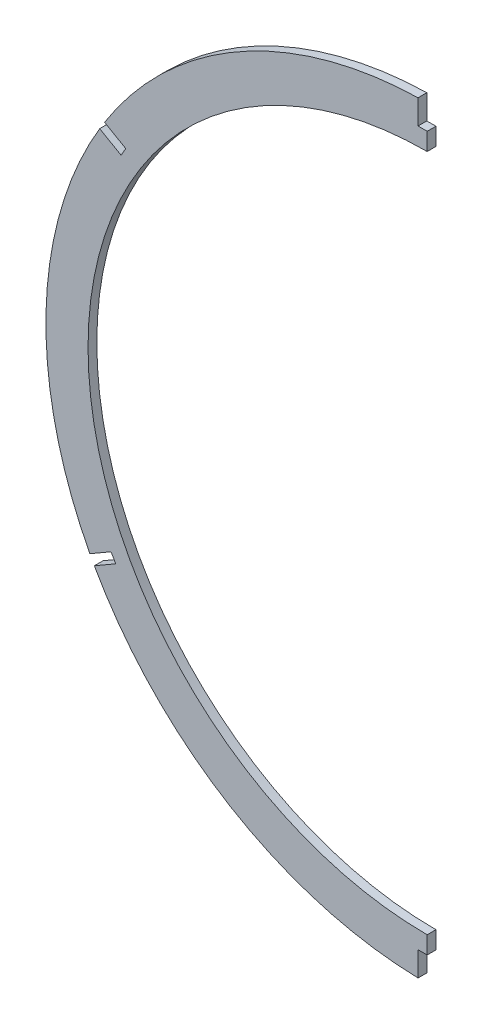
SolidWorks part; units mm, degrees
material "Balsa"
ref_plane "Front Plane" through (0, 0, 0) normal (0, 0, 1) x (1, 0, 0)
ref_plane "Top Plane" through (0, 0, 0) normal (0, 1, 0) x (1, 0, 0)
ref_plane "Right Plane" through (0, 0, 0) normal (1, 0, 0) x (0, 0, -1)
sketch "Sketch1" plane through (0, 0, 0) normal (0, 0, 1) x (1, 0, 0)
  line L0 (0, 0) -> (0, 499.9473) construction
  line L1 (0, -114.7984) -> (0, -129.4545) construction
  line L2 (0, -374.4718) -> (0, 404.2655) construction
  line L3 (-1.651, 142.9921) -> (-1.651, 150.6121) construction
  line L4 (1.651, 142.9921) -> (1.651, 150.6121) construction
  line L5 (-1.651, 142.9921) -> (1.651, 142.9921) construction
  line L6 (136.2041, -53.806) -> (0.0002, 24.7625) construction
  line L7 (-136.2076, -53.7991) -> (0.0002, 24.7625) construction
  line L8 (136.2041, -53.806) -> (0.0002, 24.7625) construction
  line L9 (-136.2076, -53.7991) -> (0.0002, 24.7625) construction
  line L10 (-125.0584, -45.4626) -> (-118.4576, -41.6554) construction
  line L11 (-123.6259, -48.4483) -> (-116.8078, -44.5157) construction
  line L12 (-118.4576, -41.6554) -> (-116.8078, -44.5157) construction
  line L13 (-124.1455, -48.7479) -> (-123.6847, -48.4822) construction
  line L14 (-123.6847, -48.4822) -> (-123.6259, -48.4483) construction
  line L15 (-125.7952, -45.8876) -> (-125.1113, -45.4931) construction
  line L16 (-125.1113, -45.4931) -> (-125.0584, -45.4626) construction
  line L17 (125.4797, -45.7137) -> (125.1075, -45.499) construction
  line L18 (123.8298, -48.5739) -> (123.6807, -48.488) construction
  line L19 (117.0223, -44.647) -> (118.6722, -41.7868) construction
  line L20 (123.6807, -48.488) -> (123.6228, -48.4545) construction
  line L21 (123.6228, -48.4545) -> (117.0223, -44.647) construction
  line L22 (125.1075, -45.499) -> (125.0554, -45.4689) construction
  line L23 (125.0554, -45.4689) -> (118.6722, -41.7868) construction
  line L24 (-107.079, -46.8884) -> (-120.3798, -54.5735)
  line L25 (-108.6638, -44.1348) -> (-121.9647, -51.8199)
  line L28 (-115.4206, -47.9666) -> (-121.9445, -51.7361) construction
  line L29 (-120.2754, -54.5131) -> (-108.646, -44.1245) construction
  line L30 (-114.4607, -49.3188) -> (-122.1124, -53.7399) construction
  line L31 (-113.7686, -50.8257) -> (-120.3665, -54.6379) construction
  line L32 (-115.4206, -47.9666) -> (-113.7686, -50.8257) construction
  line L33 (106.3137, -46.4532) -> (129.9098, -60.0883)
  line L34 (107.9004, -43.7007) -> (131.505, -57.3407)
  line L35 (129.9098, -60.0883) -> (131.505, -57.3407)
  line L36 (129.9098, -60.0883) -> (131.505, -57.3407) construction
  line L37 (107.9004, -43.7007) -> (131.505, -57.3407) construction
  line L38 (106.3137, -46.4532) -> (129.9098, -60.0883) construction
  line L39 (129.9098, -60.0883) -> (107.9004, -43.7007) construction
  line L40 (118.9051, -51.8945) -> (101.8722, -42.0519) construction
  line L41 (120.3631, -54.6438) -> (113.7655, -50.8313)
  line L42 (122.0152, -51.7848) -> (122.0057, -51.7794) construction
  line L43 (113.7655, -50.8313) -> (115.4176, -47.9723)
  line L44 (122.0057, -51.7794) -> (121.9413, -51.7421) construction
  line L45 (121.9413, -51.7421) -> (115.4176, -47.9723)
  line L46 (-108.6638, -44.1348) -> (-121.9647, -51.8199)
  line L47 (-107.079, -46.8884) -> (-120.3798, -54.5735)
  arc A0 (-1.651, 150.6121) -> (-125.0584, -45.4626) centre (0, 12.7) ccw
  circle A1 centre (0, 12.7) radius 120.904
  arc A2 (0, 150.622) -> (-1.651, 150.6121) centre (0, 12.7) ccw
  circle A3 centre (0, 12.7) radius 137.922 construction
  arc A4 (1.651, 150.6121) -> (0, 150.622) centre (0, 12.7) ccw
  arc A5 (-124.3508, -46.9604) -> (-123.6259, -48.4483) centre (0, 12.7) ccw
  arc A6 (-123.6259, -48.4483) -> (-121.9445, -51.7361) centre (0, 12.7) ccw
  arc A7 (-125.0584, -45.4626) -> (-124.3508, -46.9604) centre (0, 12.7) ccw
  arc A8 (124.3477, -46.9667) -> (125.0554, -45.4689) centre (0, 12.7) ccw
  arc A9 (125.0554, -45.4689) -> (1.651, 150.6121) centre (0, 12.7) ccw
  arc A10 (123.6228, -48.4545) -> (124.3477, -46.9667) centre (0, 12.7) ccw
  arc A11 (-121.9153, -51.7914) -> (-121.1641, -53.1919) centre (0, 12.7) ccw
  arc A12 (-120.3665, -54.6379) -> (120.3631, -54.6438) centre (0, 12.7) ccw
  arc A13 (-121.9445, -51.7361) -> (-121.9153, -51.7914) centre (0, 12.7) ccw
  arc A14 (-121.1641, -53.1919) -> (-120.3827, -54.6089) centre (0, 12.7) ccw
  arc A15 (-120.3827, -54.6089) -> (-120.397, -54.5834) centre (0, 12.7) ccw construction
  arc A16 (-120.397, -54.5834) -> (-120.3665, -54.6379) centre (0, 12.7) ccw construction
  arc A17 (120.3936, -54.5893) -> (121.0149, -53.4654) centre (0, 12.7) ccw construction
  arc A18 (121.9413, -51.7421) -> (123.6228, -48.4545) centre (0, 12.7) ccw
  arc A19 (120.3631, -54.6438) -> (120.3936, -54.5893) centre (0, 12.7) ccw construction
  arc A20 (121.0149, -53.4654) -> (121.9121, -51.7974) centre (0, 12.7) ccw construction
  arc A21 (121.9121, -51.7974) -> (121.9413, -51.7421) centre (0, 12.7) ccw construction
  spline S0 degree 3 poles (106.3137, -46.4532) (106.8426, -45.5357) (107.3715, -44.6182) (107.9004, -43.7007) knots 0 0 0 0 1 1 1 1 weights 1 1 1 1
  spline S1 degree 3 poles (-66.0123, 133.6164) (-70.0128, 131.4329) (-73.8716, 129.0699) (-81.3156, 123.9975) (-84.9009, 121.288) (-91.7995, 115.5249) (-95.113, 112.4712) (-99.0811, 108.4341) (-99.866, 107.6157) (-101.4182, 105.9565) (-102.1865, 105.1147) (-104.4569, 102.5643) (-105.9223, 100.8334) (-110.1768, 95.5512) (-115.4725, 88.2691) (-120.0285, 80.5179) (-123.1654, 74.5269) (-124.1643, 72.5002) (-125.5914, 69.415) (-126.0551, 68.3791) (-126.9587, 66.292) (-127.3989, 65.2397) (-129.5278, 59.9684) (-131.0098, 55.7) (-133.5456, 47.0638) (-134.5993, 42.696) (-136.2795, 33.8613) (-136.906, 29.3944) (-137.415, 23.7472) (-137.5031, 22.6146) (-137.6514, 20.3429) (-137.7116, 19.2049) (-137.8496, 15.7999) (-137.8852, 13.5361) (-137.8263, 6.7629) (-137.3062, -2.2197) (-135.9163, -11.1068) (-134.5433, -17.7359) (-134.0304, -19.9395) (-132.8922, -24.3345) (-132.2653, -26.5303) (-130.2347, -33.03) (-128.6774, -37.2656) (-126.1245, -43.2881) (-125.286, -45.1501) (-124.4066, -46.9926) knots 0 0 0 0 0.03125 0.03125 0.0625 0.0625 0.09375 0.09375 0.101563 0.101563 0.109375 0.109375 0.125 0.125 0.15625 0.1875 0.1875 0.203125 0.203125 0.210938 0.210938 0.21875 0.21875 0.25 0.25 0.28125 0.28125 0.3125 0.3125 0.320313 0.320313 0.328125 0.328125 0.34375 0.34375 0.375 0.40625 0.40625 0.421875 0.421875 0.4375 0.4375 0.46875 0.46875 0.48295 0.48295 0.48295 0.48295 construction
  spline S2 degree 3 poles (-2953.7904, 2461.9899) (-820.777, 189.8449) (-138.9507, -249.535) (81.4542, -98.9353) (85.033, -96.2237) (91.9188, -90.4573) (95.2258, -87.4025) (99.1858, -83.3647) (99.9691, -82.5461) (101.5182, -80.8868) (102.2849, -80.0449) (104.5506, -77.4941) (106.013, -75.7632) (110.2586, -70.4809) (112.9006, -66.8403) (117.8152, -59.3254) (120.0877, -55.4512) (123.2166, -49.4629) (124.2129, -47.4373) (125.6361, -44.3538) (126.0986, -43.3185) (126.9997, -41.2327) (127.4386, -40.181) (129.5618, -34.9121) (131.0396, -30.646) (133.5674, -22.0152) (134.6173, -17.6505) (136.2906, -8.8227) (136.914, -4.3596) (137.4197, 1.2823) (137.5071, 2.4139) (137.6542, 4.6834) (137.7138, 5.8206) (137.85, 9.2232) (137.8846, 11.4853) (137.8228, 18.2533) (137.2995, 27.2283) (135.9081, 36.1069) (134.5347, 42.7292) (134.0218, 44.9305) (132.8839, 49.3207) (132.2571, 51.5145) (130.2267, 58.0093) (128.67, 62.2416) (125.1615, 70.5162) (123.2097, 74.5586) (118.9108, 82.4534) (116.5637, 86.3058) (113.3753, 90.999) (112.7241, 91.9325) (111.3996, 93.7822) (110.7272, 94.697) (108.6802, 97.4113) (107.2757, 99.181) (102.9447, 104.3725) (96.8571, 110.9816) (90.1513, 116.9722) (84.8861, 121.2292) (83.0917, 122.6088) (80.3399, 124.6181) (79.4113, 125.2786) (77.543, 126.5731) (76.6028, 127.2075) (71.8708, 130.3161) (67.9881, 132.6004) (60.0328, 136.7739) (55.9603, 138.6631) (47.6249, 142.0446) (43.3619, 143.537) (37.9102, 145.1462) (36.8136, 145.4551) (34.6205, 146.0438) (33.5224, 146.3241) (30.2234, 147.1229) (28.0179, 147.5997) (21.3832, 148.8649) (16.9358, 149.4889) (7.993, 150.3014) (3.4975, 150.4899) (-3.2824, 150.4396) (-5.5486, 150.3672) (-10.0934, 150.1088) (-12.3559, 149.9236) (-19.101, 149.2046) (-23.5473, 148.5072) (-32.3412, 146.6856) (-36.6887, 145.5614) (-43.1354, 143.5526) (-45.2718, 142.8291) (-49.5193, 141.273) (-51.6323, 140.4395) (-369.2659, 5.9249) (-132.0865, -1278.1783) (677.8124, -3754.3927) knots -1.791229 -1.791229 -1.791229 -1.791229 0.03125 0.03125 0.0625 0.0625 0.09375 0.09375 0.101563 0.101563 0.109375 0.109375 0.125 0.125 0.15625 0.15625 0.1875 0.1875 0.203125 0.203125 0.210938 0.210938 0.21875 0.21875 0.25 0.25 0.28125 0.28125 0.3125 0.3125 0.320313 0.320313 0.328125 0.328125 0.34375 0.34375 0.375 0.40625 0.40625 0.421875 0.421875 0.4375 0.4375 0.46875 0.46875 0.5 0.5 0.53125 0.53125 0.539062 0.539062 0.546875 0.546875 0.5625 0.5625 0.59375 0.625 0.625 0.640625 0.640625 0.648437 0.648437 0.65625 0.65625 0.6875 0.6875 0.71875 0.71875 0.75 0.75 0.757812 0.757812 0.765625 0.765625 0.78125 0.78125 0.8125 0.8125 0.84375 0.84375 0.859375 0.859375 0.875 0.875 0.90625 0.90625 0.9375 0.9375 0.953125 0.953125 0.96875 0.96875 3.320852 3.320852 3.320852 3.320852 only from (66.1767, -108.566) to (-66.0123, 133.6164)
  spline S3 degree 3 poles (66.1767, -108.566) (70.1708, -106.3789) (74.0231, -104.0129) (81.4542, -98.9353) (85.033, -96.2237) (91.9188, -90.4573) (95.2258, -87.4025) (99.1858, -83.3647) (99.9691, -82.5461) (101.5182, -80.8868) (102.2849, -80.0449) (104.5506, -77.4941) (106.013, -75.7632) (110.2586, -70.4809) (112.9006, -66.8403) (117.8152, -59.3254) (120.0877, -55.4512) (123.2166, -49.4629) (124.2129, -47.4373) (125.6361, -44.3538) (126.0986, -43.3185) (126.9997, -41.2327) (127.4386, -40.181) (129.5618, -34.9121) (131.0396, -30.646) (133.5674, -22.0152) (134.6173, -17.6505) (136.2906, -8.8227) (136.914, -4.3596) (137.4197, 1.2823) (137.5071, 2.4139) (137.6542, 4.6834) (137.7138, 5.8206) (137.85, 9.2232) (137.8846, 11.4853) (137.8228, 18.2533) (137.2995, 27.2283) (135.9081, 36.1069) (134.5347, 42.7292) (134.0218, 44.9305) (132.8839, 49.3207) (132.2571, 51.5145) (130.2267, 58.0093) (128.67, 62.2416) (125.1615, 70.5162) (123.2097, 74.5586) (118.9108, 82.4534) (116.5637, 86.3058) (113.3753, 90.999) (112.7241, 91.9325) (111.3996, 93.7822) (110.7272, 94.697) (108.6802, 97.4113) (107.2757, 99.181) (102.9447, 104.3725) (96.8571, 110.9816) (90.1513, 116.9722) (84.8861, 121.2292) (83.0917, 122.6088) (80.3399, 124.6181) (79.4113, 125.2786) (77.543, 126.5731) (76.6028, 127.2075) (71.8708, 130.3161) (67.9881, 132.6004) (60.0328, 136.7739) (55.9603, 138.6631) (47.6249, 142.0446) (43.3619, 143.537) (37.9102, 145.1462) (36.8136, 145.4551) (34.6205, 146.0438) (33.5224, 146.3241) (30.2234, 147.1229) (28.0179, 147.5997) (21.3832, 148.8649) (16.9358, 149.4889) (7.993, 150.3014) (3.4975, 150.4899) (-3.2824, 150.4396) (-5.5486, 150.3672) (-10.0934, 150.1088) (-12.3559, 149.9236) (-19.101, 149.2046) (-23.5473, 148.5072) (-32.3412, 146.6856) (-36.6887, 145.5614) (-43.1354, 143.5526) (-45.2718, 142.8291) (-49.5193, 141.273) (-51.6323, 140.4395) (-57.9206, 137.7764) (-62.0153, 135.798) (-66.0123, 133.6164) knots 0 0 0 0 0.03125 0.03125 0.0625 0.0625 0.09375 0.09375 0.101563 0.101563 0.109375 0.109375 0.125 0.125 0.15625 0.15625 0.1875 0.1875 0.203125 0.203125 0.210938 0.210938 0.21875 0.21875 0.25 0.25 0.28125 0.28125 0.3125 0.3125 0.320313 0.320313 0.328125 0.328125 0.34375 0.34375 0.375 0.40625 0.40625 0.421875 0.421875 0.4375 0.4375 0.46875 0.46875 0.5 0.5 0.53125 0.53125 0.539062 0.539062 0.546875 0.546875 0.5625 0.5625 0.59375 0.625 0.625 0.640625 0.640625 0.648437 0.648437 0.65625 0.65625 0.6875 0.6875 0.71875 0.71875 0.75 0.75 0.757812 0.757812 0.765625 0.765625 0.78125 0.78125 0.8125 0.8125 0.84375 0.84375 0.859375 0.859375 0.875 0.875 0.90625 0.90625 0.9375 0.9375 0.953125 0.953125 0.96875 0.96875 1 1 1 1 construction
  spline S4 degree 3 poles (-124.4066, -46.9926) (-124.169, -47.4906) (-123.9283, -47.9871) (-123.6847, -48.4822) knots 0.48295 0.48295 0.48295 0.48295 0.486788 0.486788 0.486788 0.486788 construction
  spline S5 degree 3 poles (-123.6847, -48.4822) (-122.846, -50.1865) (-121.9718, -51.874) (-118.9108, -57.4955) (-116.5612, -61.3517) (-113.369, -66.0497) (-112.7169, -66.9844) (-111.3913, -68.8351) (-110.7184, -69.7503) (-108.6697, -72.4662) (-107.264, -74.2369) (-102.929, -79.4315) (-96.8353, -86.0447) (-90.1214, -92.0392) (-84.8493, -96.299) (-83.0524, -97.6795) (-80.2967, -99.6899) (-79.367, -100.3507) (-77.4971, -101.6451) (-76.5559, -102.2795) (-71.8198, -105.3881) (-67.9332, -107.6723) (-59.9695, -111.8452) (-55.8924, -113.7339) (-47.5468, -117.114) (-43.2782, -118.6053) (-37.8188, -120.2127) (-36.7216, -120.521) (-34.5268, -121.1085) (-33.4279, -121.3881) (-30.1264, -122.185) (-27.9191, -122.6605) (-21.2788, -123.9216) (-16.8274, -124.5426) (-7.8757, -125.3484) (-3.3755, -125.5332) (3.4122, -125.4766) (5.6812, -125.4019) (10.231, -125.1387) (12.493, -124.9512) (19.2413, -124.2249) (23.6899, -123.5224) (32.4889, -121.6898) (36.8393, -120.5597) (43.2904, -118.5412) (45.4283, -117.8143) (48.6163, -116.6419) (49.6759, -116.2374) (51.7885, -115.4006) (52.8426, -114.968) (58.0839, -112.7404) (62.1792, -110.755) (66.1767, -108.566) knots 0.486788 0.486788 0.486788 0.486788 0.5 0.5 0.53125 0.53125 0.539062 0.539062 0.546875 0.546875 0.5625 0.5625 0.59375 0.625 0.625 0.640625 0.640625 0.648437 0.648437 0.65625 0.65625 0.6875 0.6875 0.71875 0.71875 0.75 0.75 0.757812 0.757812 0.765625 0.765625 0.78125 0.78125 0.8125 0.8125 0.84375 0.84375 0.859375 0.859375 0.875 0.875 0.90625 0.90625 0.9375 0.9375 0.953125 0.953125 0.960937 0.960937 0.96875 0.96875 1 1 1 1 construction
  spline S6 degree 3 poles (-108.6638, -44.1348) (-108.1355, -45.0527) (-107.6073, -45.9705) (-107.079, -46.8884) knots 0 0 0 0 1 1 1 1 weights 1 1 1 1
  spline S7 degree 3 poles (-121.9647, -51.8199) (-121.4364, -52.7377) (-120.9081, -53.6556) (-120.3798, -54.5735) knots 0 0 0 0 1 1 1 1 weights 1 1 1 1
  spline S8 degree 3 poles (-1893.2868, -3504.9508) (-555.1038, -1197.2913) (777.7443, 1114.8675) (2098.5226, 3419.8495) knots -1257.715582 -1257.715582 -1257.715582 -1257.715582 1261.2826 1261.2826 1261.2826 1261.2826 weights 1.001261 0.999578 0.99958 1.001266 only from (106.3137, -46.4532) to (107.9004, -43.7007)
  spline S9 degree 3 poles (-121.8597, -51.7592) (-121.5948, -52.2177) (-121.3299, -52.6762) (-121.065, -53.1347) knots 0 0 0 0 0.5 0.5 0.5 0.5 weights 1 1 1 1 construction
  spline S12 degree 3 poles (-2107.5184, 3411.1282) (-794.411, 1112.1626) (537.2029, -1201.4874) (1876.5356, -3511.0638) knots -1261.624621 -1261.624621 -1261.624621 -1261.624621 1257.384167 1257.384167 1257.384167 1257.384167 weights 1.00204 0.999326 0.99932 1.002023 only from (-121.9647, -51.8199) to (-120.3798, -54.5735)
  spline S13 degree 3 poles (-2094.7969, 3419.3607) (-780.7303, 1119.4679) (550.7427, -1194.0569) (1889.8709, -3504.2883) knots -1261.518414 -1261.518414 -1261.518414 -1261.518414 1257.484402 1257.484402 1257.484402 1257.484402 weights 1.00184 0.999392 0.999387 1.001825 only from (-108.6638, -44.1348) to (-107.079, -46.8884)
  point P7 (0, -125.5003)
  point P8 (0, 150.4602)
  point P25 (-125.0584, -45.4626)
  point P38 (123.6228, -48.4545)
  dimension "D2" = 275.844
  dimension "D1" = 275.9605
  dimension "D3" = 12.7
  dimension "D5" = 3.302
  dimension "D6" = 7.62
  dimension "D7" = 3.302
  dimension "D8" = 7.62
  dimension "D9" = 3.302
  dimension "D10" = 7.62
  dimension "D11" = 3.302
  dimension "D12" = 7.62
  dimension "D13" = 3.302
  dimension "D14" = 7.62
  dimension "D4" = 17.018
sketch "Sketch2" plane through (248.2736, -245.0135, 0) normal (0, 0, -1) x (0, -1, 0)
  line L3 (-245.0135, 248.2736) -> (-427.6569, 248.2736) construction
  circle A1 centre (-257.7135, 248.2736) radius 137.922
  circle A16 centre (-257.7135, 248.2736) radius 122.682
  dimension "D1" = 12.7
  dimension "D2" = 275.844
  dimension "D3" = 15.24
extrude "Boss-Extrude2" add sketch "Sketch2" along normal mid plane 3.175
sketch "Sketch3" plane through (0, 0, 0) normal (1, 0, 0) x (0, 0, -1)
  line L1 (-141.282, 263.3615) -> (149.6958, 263.3615)
  line L2 (-141.282, 263.3615) -> (-141.282, -241.4673)
  line L3 (-141.282, -241.4673) -> (149.6958, -241.4673)
  line L4 (149.6958, 263.3615) -> (149.6958, -241.4673)
extrude "Cut-Extrude1" cut sketch "Sketch3" along normal through all
sketch "Sketch5" plane through (0, 0, 1.5875) normal (0, 0, 1) x (1, 0, 0)
  line L0 (0, 0) -> (0, 135.382) construction
  line L1 (0, 135.382) -> (0, 141.732) construction
  line L2 (-3.302, 141.732) -> (3.302, 141.732)
  line L3 (0, 141.732) -> (0, 151.892)
  line L4 (-3.302, 151.892) -> (3.302, 151.892)
  line L5 (3.302, 141.732) -> (3.302, 151.892)
  line L6 (103.544, 78.6136) -> (105.2331, 75.688) construction
  line L7 (104.3885, 77.1508) -> (0, 16.882) construction
  line L8 (103.544, 78.6136) -> (105.2331, 75.688) construction
  line L9 (103.544, 78.6136) -> (109.0433, 81.7886) construction
  line L10 (105.2331, 75.688) -> (110.7324, 78.863) construction
  line L11 (109.0433, 81.7886) -> (110.7324, 78.863) construction
  line L12 (109.0433, 81.7886) -> (110.7324, 78.863)
  line L13 (109.0433, 81.7886) -> (118.3449, 87.1589)
  line L14 (110.7324, 78.863) -> (120.034, 84.2333)
  line L15 (118.3449, 87.1589) -> (120.034, 84.2333)
  line L16 (0, 16.882) -> (0, -109.982) construction
  line L17 (0, -109.982) -> (0, -116.332) construction
  line L18 (-3.302, -116.332) -> (3.302, -116.332)
  line L19 (0, -116.332) -> (0, -126.6527)
  line L20 (-3.302, -126.6527) -> (3.302, -126.6527)
  line L21 (3.302, -116.332) -> (3.302, -126.6527)
  line L22 (107.1657, -46.9405) -> (108.8548, -44.0149) construction
  line L23 (108.0103, -45.4777) -> (0, 16.882) construction
  line L24 (107.1657, -46.9405) -> (108.8548, -44.0149) construction
  line L25 (107.1657, -46.9405) -> (112.665, -50.1155) construction
  line L26 (108.8548, -44.0149) -> (114.3541, -47.1899) construction
  line L27 (112.665, -50.1155) -> (114.3541, -47.1899) construction
  line L28 (112.665, -50.1155) -> (114.3541, -47.1899)
  line L29 (112.665, -50.1155) -> (134.6621, -62.8155)
  line L30 (114.3541, -47.1899) -> (136.3512, -59.8899)
  line L31 (134.6621, -62.8155) -> (136.3512, -59.8899)
  line L32 (-112.665, -50.1155) -> (-114.3541, -47.1899) construction
  line L33 (-108.8548, -44.0149) -> (-114.3541, -47.1899) construction
  line L34 (-107.1657, -46.9405) -> (-112.665, -50.1155) construction
  line L35 (-107.1657, -46.9405) -> (-108.8548, -44.0149) construction
  line L36 (-108.0103, -45.4777) -> (0, 16.882) construction
  line L37 (-107.1657, -46.9405) -> (-108.8548, -44.0149) construction
  line L38 (-109.0433, 81.7886) -> (-110.7324, 78.863) construction
  line L39 (-105.2331, 75.688) -> (-110.7324, 78.863) construction
  line L40 (-103.544, 78.6136) -> (-109.0433, 81.7886) construction
  line L41 (-103.544, 78.6136) -> (-105.2331, 75.688) construction
  line L42 (-104.3885, 77.1508) -> (0, 16.882) construction
  line L43 (-103.544, 78.6136) -> (-105.2331, 75.688) construction
  line L44 (-134.6621, -62.8155) -> (-136.3512, -59.8899)
  line L45 (-114.3541, -47.1899) -> (-136.3512, -59.8899)
  line L46 (-112.665, -50.1155) -> (-134.6621, -62.8155)
  line L47 (-112.665, -50.1155) -> (-114.3541, -47.1899)
  line L48 (-3.302, -116.332) -> (-3.302, -126.6527)
  line L49 (-118.3449, 87.1589) -> (-120.034, 84.2333)
  line L50 (-110.7324, 78.863) -> (-120.034, 84.2333)
  line L51 (-109.0433, 81.7886) -> (-118.3449, 87.1589)
  line L52 (-109.0433, 81.7886) -> (-110.7324, 78.863)
  line L53 (-3.302, 141.732) -> (-3.302, 151.892)
  point P9 (104.3885, 77.1508)
  point P19 (108.0103, -45.4777)
  point P28 (0, 0)
  point P29 (0, 0)
  point P30 (0, 0)
  point P31 (0, 0)
  point P51 (-104.8204, 77.4001)
  point P52 (-104.9805, 77.4926)
  line M25 (0, 135.382) -> (0, 150.622)
  arc M26 (0, 150.622) -> (0, -125.222) centre (0, 12.7) ccw
  line M27 (0, -125.222) -> (0, -109.982)
  dimension "D1" = 16.882
  dimension "D2" = 60
  dimension "D3" = 60
  dimension "D4" = 135.382
  dimension "D5" = 120.5375
  dimension "D6" = 124.7195
  dimension "D7" = 126.864
  dimension "D8" = 6.35
  dimension "D9" = 6.35
  dimension "D10" = 10.7406
  dimension "D11" = 3.3782
  dimension "D12" = 6.35
  dimension "D13" = 3.3782
  dimension "D14" = 6.35
  dimension "D15" = 3.302
  dimension "D16" = 10.3207
  dimension "D17" = 3.302
extrude "Cut-Extrude2" cut sketch "Sketch5" against normal through all contours L53 L2 M25 M26 | L52 L51 L50 M26 | L46 L47 L45 M26 | L18 L48 M26 M27 region at (-1.6498, 146.1704, 1.5875) region at (-1.6498, -120.7704, 1.5875) region at (-117.3587, -50.8783, 1.5875) region at (-113.7398, 82.5465, 1.5875)
equation "\"slotwidth\"=0.13"
equation "\"D11@Sketch1\"=\"slotwidth\""
